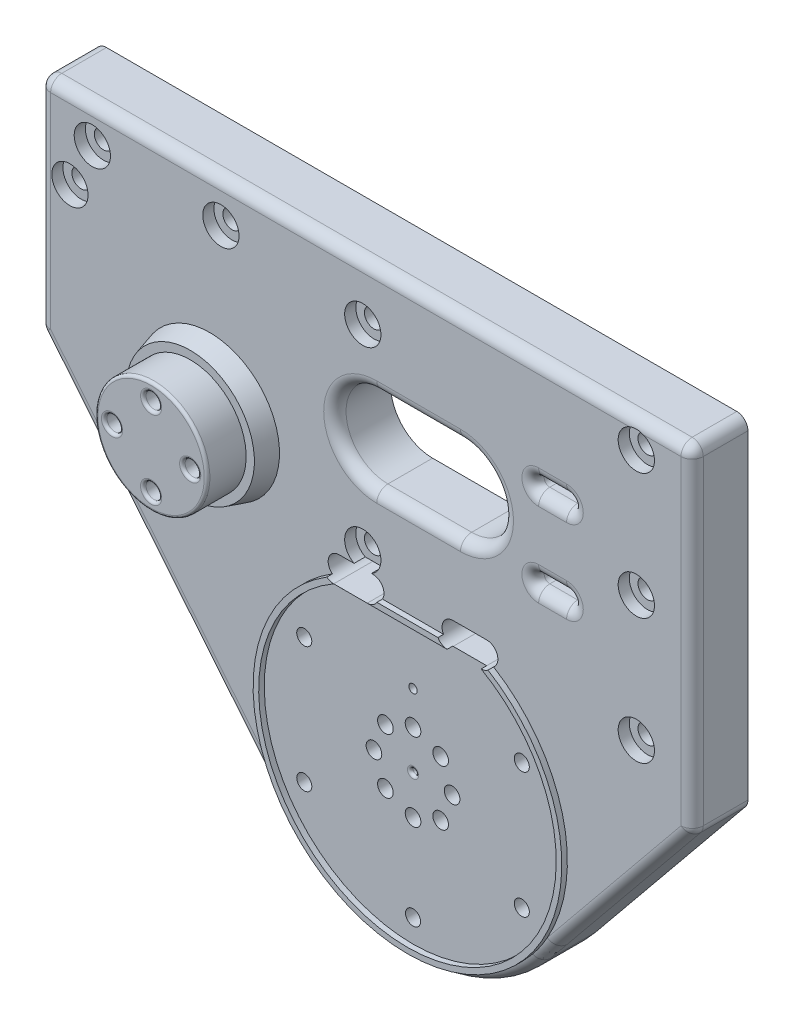
SolidWorks part; units mm, degrees
ref_plane "Front Plane" through (0, 0, 0) normal (0, 0, 1) x (1, 0, 0)
ref_plane "Top Plane" through (0, 0, 0) normal (0, 1, 0) x (1, 0, 0)
ref_plane "Right Plane" through (0, 0, 0) normal (1, 0, 0) x (0, 0, -1)
sketch "Sketch1" plane through (0, 0, 0) normal (0, 0, 1) x (1, 0, 0)
  line L0 (-36.42, 37.54) -> (-36.42, 0) construction
  line L1 (-66.92, 75) -> (50, 75)
  line L2 (-66.92, 75) -> (-66.92, -30)
  line L3 (-66.92, -30) -> (50, -30)
  line L4 (50, 75) -> (50, -30)
  line L5 (-36.42, 0) -> (0, 0) construction
  circle A0 centre (0, 0) radius 0.5
  circle A1 centre (-36.42, 37.54) radius 0.5
  dimension "D1" = 1
  dimension "D2" = 1
  dimension "D3" = 36.42
  dimension "D4" = 37.54
  dimension "D5" = 50
  dimension "D6" = 30
  dimension "D7" = 30
  dimension "D8" = 37.46
extrude "Boss-Extrude1" add sketch "Sketch1" along normal blind 10
ref_axis "Axis1" through (-36.42, 37.54, 10) along (0, 0, -1)
ref_plane "Plane1" through (0, 37.54, 0) normal (0, 1, 0) x (0, 0, -1)
sketch "Sketch5" plane through (0, 37.54, 0) normal (0, 1, 0) x (0, 0, -1)
  line L0 (-10, 36.92) -> (-10, 35.92) construction
  line L1 (-10, 36.92) -> (-10, 35.92) construction
  line L2 (-10, 36.42) -> (-20.5, 36.42) construction
  line L3 (-20.5, 36.42) -> (-20.5, 26.395)
  line L4 (-20.5, 26.395) -> (-13.5, 26.395)
  line L5 (-13.5, 26.395) -> (-13.5, 24.92)
  line L6 (-13.5, 24.92) -> (-10, 23.92)
  line L7 (-10, 66.92) -> (-10, -50) construction
  line L8 (-10, 36.42) -> (-10, 23.92)
  line L9 (-10, 36.42) -> (-20.5, 36.42)
  line L11 (-13.5, 108.28) -> (-13.5, 138.68) construction
  dimension "D1" = 23
  dimension "D2" = 20.05
  dimension "D3" = 7
  dimension "D4" = 12.5
  dimension "D5" = 3.5
revolve "Revolve1" add sketch "Sketch5" angle 360 about L9
sketch "Sketch6" plane through (0, 0, 20.5) normal (0, 0, 1) x (1, 0, 0)
  line L0 (-36.42, 37.54) -> (-36.42, 44.54) construction
  circle A0 centre (-36.42, 44.54) radius 1.4
  circle A1 centre (-29.42, 37.54) radius 1.4
  circle A2 centre (-36.42, 30.54) radius 1.4
  circle A3 centre (-43.42, 37.54) radius 1.4
  point P13 (-36.42, 37.54)
  dimension "D1" = 7
  dimension "D2" = 2.8
  dimension "D3" = 4
extrude "Cut-Extrude1" cut sketch "Sketch6" against normal through all
sketch "Sketch10" plane through (0, 0, 0) normal (0, 0, -1) x (-1, 0, 0)
  circle A0 centre (0, 0) radius 22.5 construction
  circle A1 centre (-19.484, 11.2528) radius 1.35
  arc A7 (-19.4838, 12.2778) -> (-19.4841, 10.2278) centre (-19.484, 11.2528) ccw construction
  arc A8 (-19.4838, 12.2778) -> (-19.4841, 10.2278) centre (-19.484, 11.2528) ccw construction
  arc A9 (19.4873, 12.2722) -> (19.487, 10.2222) centre (19.4872, 11.2472) ccw construction
  arc A10 (19.4841, -10.2278) -> (19.4838, -12.2778) centre (19.484, -11.2528) ccw construction
  arc A11 (-0.0031, -21.475) -> (-0.0033, -23.525) centre (-0.0032, -22.5) ccw construction
  arc A12 (-19.487, -10.2222) -> (-19.4873, -12.2722) centre (-19.4872, -11.2472) ccw construction
  arc A13 (19.4873, 12.2722) -> (19.487, 10.2222) centre (19.4872, 11.2472) ccw construction
  arc A14 (19.4841, -10.2278) -> (19.4838, -12.2778) centre (19.484, -11.2528) ccw construction
  arc A15 (-0.0031, -21.475) -> (-0.0033, -23.525) centre (-0.0032, -22.5) ccw construction
  arc A16 (-19.487, -10.2222) -> (-19.4873, -12.2722) centre (-19.4872, -11.2472) ccw construction
  circle A17 centre (-19.4872, -11.2472) radius 1.35
  circle A18 centre (-0.0032, -22.5) radius 1.35
  circle A19 centre (19.484, -11.2528) radius 1.35
  circle A20 centre (19.4872, 11.2472) radius 1.35
  point P17 (0, 0)
  dimension "D1" = 45
  dimension "D2" = 2.7
extrude "Ak45 holes" cut sketch "Sketch10" against normal through all
fillet "Fillet3" radius 0.5 6 edges at (-46.445, 37.54, 20.5) (-42.02, 37.54, 20.5) (-35.02, 30.54, 20.5) (-28.02, 37.54, 20.5) (-35.02, 44.54, 20.5) (0.5, 0, 10)
hole_wizard "CBORE for M5 Hex Head Bolt1" positions "3DSketch1" profile "Sketch14" counterbore size "M5" standard "ANSI Metric" end condition through all
sketch3d "3DSketch1"
  line L4 (19.484, 11.2528, 10) -> (19.484, 11.2528, 0) construction
  line L5 (19.4872, -11.2472, 10) -> (19.4872, -11.2472, 0) construction
  line L6 (0.0032, -22.5, 10) -> (0.0032, -22.5, 0) construction
  line L7 (-19.484, -11.2528, 10) -> (-19.484, -11.2528, 0) construction
  line L8 (-19.4872, 11.2472, 10) -> (-19.4872, 11.2472, 0) construction
  point P16 (19.484, 11.2528, 0)
  point P30 (19.4872, -11.2472, 0)
  point P34 (0.0032, -22.5, 0)
  point P38 (-19.484, -11.2528, 0)
  point P42 (-19.4872, 11.2472, 0)
sketch "Sketch14" plane through (19.484, 11.2528, 0) normal (1, 0, 0) x (0, 1, 0)
  line L0 (0, 0) -> (0, 20.5)
  line L1 (0, 20.5) -> (1.35, 20.5)
  line L3 (1.35, 20.5) -> (1.35, 2.5)
  line L4 (1.35, 2.5) -> (2.75, 2.5)
  line L5 (2.75, 2.5) -> (2.75, 0)
  line L7 (2.75, 0) -> (0, 0)
  line L11 (0, -6.35) -> (0, 107.95) construction
  dimension "Thru Hole Dia." = 2.7
  dimension "Thru Hole Depth" = 20.5
  dimension "C'Bore Dia." = 5.5
  dimension "C'Bore Depth" = 2.5
sketch "Sketch16" plane through (0, 0, 10) normal (0, 0, 1) x (1, 0, 0)
  line L0 (13.199, 23.1519) -> (-13.2056, 23.1481)
  line L1 (-12.1276, 22.9983) -> (12.1211, 23.0017) construction
  line L3 (13.4613, 24.1519) -> (-13.4682, 24.1481)
  arc A0 (-13.2056, 23.1481) -> (13.199, 23.1519) centre (0, 0) ccw
  arc A2 (0.0038, -26.5) -> (13.1592, 23.0019) centre (0, 0) ccw construction
  arc A3 (0.0038, -26.5) -> (13.1592, 23.0019) centre (0, 0) ccw construction
  arc A4 (-13.4682, 24.1481) -> (13.4613, 24.1519) centre (0, 0) ccw
  dimension "D2" = 26.5
  dimension "D3" = 26.65
  dimension "D1" = 0.15
  dimension "D4" = 1
extrude "Boss-Extrude4" add sketch "Sketch16" along normal blind 1
sketch "Sketch17" plane through (0, 0, 10) normal (0, 0, 1) x (1, 0, 0)
  line L0 (0, 7) -> (0, 0) construction
  circle A0 centre (0, 7) radius 1.4
  circle A1 centre (4.9497, 4.9497) radius 1.4
  circle A2 centre (7, 0) radius 1.4
  circle A3 centre (4.9497, -4.9497) radius 1.4
  circle A4 centre (0, -7) radius 1.4
  circle A5 centre (-4.9497, -4.9497) radius 1.4
  circle A6 centre (-7, 0) radius 1.4
  circle A7 centre (-4.9497, 4.9497) radius 1.4
  point P13 (0, 0)
  dimension "D1" = 2.8
  dimension "D2" = 7
  dimension "D3" = 8
extrude "Cut-Extrude5" cut sketch "Sketch17" against normal through all
sketch "WheelPointTravel" plane through (0, 0, 10) normal (0, 0, 1) x (1, 0, 0)
  line L0 (-67.04, -61.85) -> (-67.04, -341.8) construction
  line L1 (-57.865, -61.85) -> (-76.215, -61.85)
  line L2 (-57.865, -61.85) -> (-57.865, -341.8)
  line L3 (-57.865, -341.8) -> (-76.215, -341.8)
  line L4 (-76.215, -61.85) -> (-76.215, -341.8)
  dimension "D1" = 67.04
  dimension "D2" = 18.35
  dimension "D3" = 61.85
  dimension "D4" = 279.95
sketch "Angle Retracted Extended" plane through (0, 0, 0) normal (0, 0, -1) x (-1, 0, 0)
  line L0 (0, 0) -> (316.0647, 168.0546) construction
  line L1 (138.3785, -213.0843) -> (0, 0) construction
  line L2 (0, 0) -> (228.0086, 0) construction
  dimension "D1" = 28
  dimension "D2" = 57
sketch "Sketch18" plane through (0, 0, 10) normal (0, 0, 1) x (1, 0, 0)
  circle A0 centre (-57.4513, 68.5011) radius 1.6 construction
  circle A6 centre (-34.4188, 67.6329) radius 1.6 construction
  circle A7 centre (-57.4513, 68.5011) radius 1.6
  circle A14 centre (40, 70) radius 1.7 construction
  circle A15 centre (40, 47.5) radius 1.7 construction
  circle A16 centre (40, 25) radius 1.7 construction
  circle A17 centre (-9, 30) radius 1.7 construction
  circle A18 centre (-9, 65) radius 1.7 construction
  circle A19 centre (40, 70) radius 1.7
  circle A20 centre (40, 47.5) radius 1.7
  circle A21 centre (40, 25) radius 1.7
  circle A22 centre (-9, 30) radius 1.7
  circle A23 centre (-9, 65) radius 1.7
  circle A24 centre (-34.4188, 67.6329) radius 1.6
  circle A26 centre (-61.4671, 60.4467) radius 1.6 construction
  circle A27 centre (-61.4671, 60.4467) radius 1.6
extrude "Fastener holes" cut sketch "Sketch18" against normal through all
hole_wizard "CBORE for M5 Hex Head Bolt2" positions "3DSketch2" profile "Sketch19" counterbore size "M5" standard "ANSI Metric" end condition through all
sketch3d "3DSketch2"
  line L0 (-57.4513, 68.5011, 0) -> (-57.4513, 68.5011, 10) construction
  line L7 (-9, 65, 0) -> (-9, 65, 10) construction
  line L8 (-9, 30, 0) -> (-9, 30, 10) construction
  line L9 (40, 25, 0) -> (40, 25, 10) construction
  line L10 (40, 47.5, 0) -> (40, 47.5, 10) construction
  line L11 (40, 70, 0) -> (40, 70, 10) construction
  line L15 (-34.4188, 67.6329, 0) -> (-34.4188, 67.6329, 10) construction
  line L16 (-61.4671, 60.4467, 0) -> (-61.4671, 60.4467, 10) construction
  point P0 (-57.4513, 68.5011, 10)
  point P29 (-34.4188, 67.6329, 10)
  point P36 (-9, 65, 10)
  point P40 (-9, 30, 10)
  point P44 (40, 25, 10)
  point P48 (40, 47.5, 10)
  point P52 (40, 70, 10)
  point P86 (-61.4671, 60.4467, 10)
sketch "Sketch19" plane through (-57.4513, 68.5011, 10) normal (1, 0, 0) x (0, -1, 0)
  line L0 (0, 0) -> (0, 10)
  line L1 (0, 10) -> (1.65, 10)
  line L3 (1.65, 10) -> (1.65, 2)
  line L4 (1.65, 2) -> (3.25, 2)
  line L5 (3.25, 2) -> (3.25, 0)
  line L7 (3.25, 0) -> (0, 0)
  line L11 (0, -6.35) -> (0, 107.95) construction
  dimension "Thru Hole Dia." = 3.3
  dimension "Thru Hole Depth" = 10
  dimension "C'Bore Dia." = 6.5
  dimension "C'Bore Depth" = 2
sketch "Sketch20" plane through (0, 0, 0) normal (0, 0, -1) x (-1, 0, 0)
  line L0 (-50, 15) -> (-22.6599, -18.4957)
  line L1 (-50, -30) -> (-50, 75) construction
  line L2 (22.6352, -18.5259) -> (66.92, 35.582)
  line L3 (0, 0) -> (316.0647, 168.0546) construction
  line L4 (66.92, 75) -> (66.92, -30) construction
  line L5 (-50, 15) -> (-50, -30)
  line L6 (-50, -30) -> (66.92, -30)
  line L7 (66.92, -30) -> (66.92, 35.582)
  arc A0 (-22.6599, -18.4957) -> (22.6352, -18.5259) centre (0, 0) ccw
  circle A1 centre (-40, 25) radius 1.7 construction
  dimension "D1" = 58.5
  dimension "D2" = 10
extrude "Cut-Extrude7" cut sketch "Sketch20" against normal through all
sketch "Sketch21" plane through (0, 0, 0) normal (0, 0, -1) x (-1, 0, 0)
  line L4 (-22.5, 39.5) -> (-27.5, 39.5) construction
  line L5 (-27.5, 41.5) -> (-22.5, 41.5) construction
  line L6 (-22.5, 54.5) -> (-27.5, 54.5) construction
  line L7 (-27.5, 56.5) -> (-22.5, 56.5) construction
  line L8 (-22.5, 39.5) -> (-27.5, 39.5)
  line L9 (-27.5, 41.5) -> (-22.5, 41.5)
  line L10 (-22.5, 54.5) -> (-27.5, 54.5)
  line L11 (-27.5, 56.5) -> (-22.5, 56.5)
  line L12 (6.5, 55.5) -> (-8.5, 55.5) construction
  line L13 (-8.5, 40.5) -> (6.5, 40.5) construction
  line L14 (6.5, 55.5) -> (-8.5, 55.5)
  line L15 (-8.5, 40.5) -> (6.5, 40.5)
  arc A4 (-22.5, 39.5) -> (-22.5, 41.5) centre (-22.5, 40.5) ccw construction
  arc A5 (-27.5, 41.5) -> (-27.5, 39.5) centre (-27.5, 40.5) ccw construction
  arc A6 (-22.5, 54.5) -> (-22.5, 56.5) centre (-22.5, 55.5) ccw construction
  arc A7 (-27.5, 56.5) -> (-27.5, 54.5) centre (-27.5, 55.5) ccw construction
  arc A8 (-22.5, 39.5) -> (-22.5, 41.5) centre (-22.5, 40.5) ccw
  arc A9 (-27.5, 41.5) -> (-27.5, 39.5) centre (-27.5, 40.5) ccw
  arc A10 (-22.5, 54.5) -> (-22.5, 56.5) centre (-22.5, 55.5) ccw
  arc A11 (-27.5, 56.5) -> (-27.5, 54.5) centre (-27.5, 55.5) ccw
  arc A12 (6.5, 40.5) -> (6.5, 55.5) centre (6.5, 48) ccw construction
  arc A13 (-8.5, 55.5) -> (-8.5, 40.5) centre (-8.5, 48) ccw construction
  arc A14 (6.5, 40.5) -> (6.5, 55.5) centre (6.5, 48) ccw
  arc A15 (-8.5, 55.5) -> (-8.5, 40.5) centre (-8.5, 48) ccw
extrude "Cable hole" cut sketch "Sketch21" against normal through all
fillet "Fillet4" radius 2 21 edges at (28.5, 55.5, 10) (25, 54.5, 10) (21.5, 55.5, 10) (28.5, 40.5, 10) (25, 39.5, 10) (21.5, 40.5, 10) (1, 55.5, 10) (-14, 48, 10) (36.33, -1.7478, 10) (25, 56.5, 10) (25, 41.5, 10) (50, 15, 5) (-66.92, 35.582, 5) (50, 75, 5) (-66.92, 75, 5) (50, 45, 10) (-44.7776, 8.5281, 10) (-66.92, 55.291, 10) (-8.46, 75, 10) (16, 48, 10) (1, 40.5, 10)
sketch "Sketch23" plane through (0, 0, 0) normal (0, 0, -1) x (-1, 0, 0)
  circle A0 centre (0, 13) radius 0.75 construction
  circle A1 centre (0, 13) radius 0.75
extrude "Cut-Extrude10" cut sketch "Sketch23" against normal through all
sketch "Sketch24" plane through (0, 0, 10) normal (0, 0, 1) x (1, 0, 0)
  line L0 (13.199, 25.149) -> (7.199, 25.149) construction
  line L1 (13.199, 23.149) -> (7.199, 23.149)
  line L2 (13.199, 27.149) -> (7.199, 27.149)
  line L3 (-13.2056, 25.149) -> (-7.2056, 25.149) construction
  line L4 (-13.2056, 27.149) -> (-7.2056, 27.149)
  line L5 (-13.2056, 23.149) -> (-7.2056, 23.149)
  line L6 (13.199, 23.1519) -> (-13.2056, 23.1481) construction
  arc A0 (13.199, 23.149) -> (13.199, 27.149) centre (13.199, 25.149) ccw
  arc A1 (7.199, 27.149) -> (7.199, 23.149) centre (7.199, 25.149) ccw
  arc A2 (-13.2056, 27.149) -> (-13.2056, 23.149) centre (-13.2056, 25.149) ccw
  arc A3 (-7.2056, 23.149) -> (-7.2056, 27.149) centre (-7.2056, 25.149) ccw
  point P2 (10.199, 25.149)
  point P7 (-10.2056, 25.149)
  dimension "D1" = 6
  dimension "D2" = 4
extrude "Cut-Extrude11" cut sketch "Sketch24" against normal through all and the other way through all
